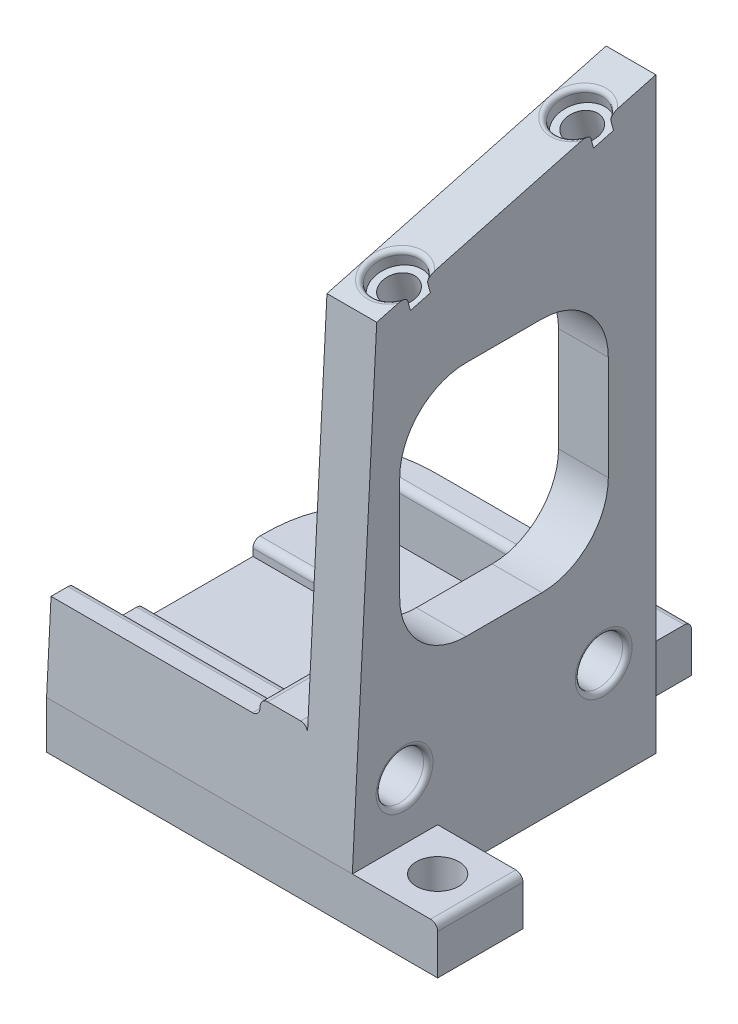
SolidWorks part; units mm, degrees
ref_plane "Front" through (0, 0, 0) normal (0, 0, 1) x (1, 0, 0)
ref_plane "Top" through (0, 0, 0) normal (0, 1, 0) x (1, 0, 0)
ref_plane "Right" through (0, 0, 0) normal (1, 0, 0) x (0, 0, -1)
sketch "Sketch1" plane through (0, 0, 0) normal (1, 0, 0) x (0, 0, -1)
  line L0 (-13.0089, 0) -> (13.0089, 0)
  line L1 (13.0089, 0) -> (13.0089, 8.5)
  line L2 (13.0089, 8.5) -> (5.7589, 8.5)
  line L3 (5.7589, 8.5) -> (5.7589, 7)
  line L4 (5.7589, 7) -> (-5.7589, 7)
  line L5 (-5.7589, 7) -> (-5.7589, 8.5)
  line L6 (-5.7589, 8.5) -> (-13.0089, 8.5)
  line L7 (-13.0089, 8.5) -> (-13.0089, 0)
  dimension "D1" = 8.5
  dimension "D2" = 7.25
  dimension "D3" = 26.0178
  dimension "D4" = 1.5
extrude "Boss-Extrude1" add sketch "Sketch1" along normal mid plane 22
sketch "Sketch3" plane through (0, 0, 0) normal (0, -1, 0) x (1, 0, 0)
  line L1 (-11, -13.0089) -> (11, -13.0089)
  line L2 (-11, -13.0089) -> (-11, -16.0089)
  line L3 (-11, -16.0089) -> (11, -16.0089)
  line L4 (11, -13.0089) -> (11, -16.0089)
  line L5 (-11, 13.0089) -> (11, 13.0089)
  line L6 (-11, 13.0089) -> (-11, 16.0089)
  line L7 (-11, 16.0089) -> (11, 16.0089)
  line L8 (11, 13.0089) -> (11, 16.0089)
  dimension "D1" = 3
  dimension "D2" = 22
  dimension "D3" = 3
  dimension "D4" = 22
extrude "Boss-Extrude2" add sketch "Sketch3" against normal blind 14
sketch "Sketch4" plane through (11, 0, 0) normal (1, 0, 0) x (0, 0, -1)
  line L0 (0, 0) -> (0, 15.7) construction
  line L1 (-16.0089, 0) -> (16.0089, 0) construction
  line L2 (-8.8, 15.7) -> (-16.0089, 15.7)
  line L3 (-16.0089, 14) -> (-16.0089, 0) construction
  line L4 (-16.0089, 15.7) -> (-16.0089, 0)
  line L5 (-16.0089, 0) -> (16.0089, 0)
  line L6 (16.0089, 0) -> (16.0089, 15.7)
  line L7 (16.0089, 14) -> (16.0089, 0) construction
  line L8 (16.0089, 15.7) -> (-8.8, 15.7)
  dimension "D2" = 15.7
extrude "Boss-Extrude3" add sketch "Sketch4" along normal blind 5
sketch "Sketch5" plane through (16, 0, 0) normal (1, 0, 0) x (0, 0, -1)
  line L0 (-16.0089, 11) -> (-10.5, 11) construction
  line L1 (-16.0089, 15.7) -> (-16.0089, 0) construction
  line L2 (-10.5, 11) -> (-10.5, 0) construction
  line L3 (-16.0089, 0) -> (16.0089, 0) construction
  line L4 (0, 0) -> (0, 15.7) construction
  line L5 (16.0089, 15.7) -> (-16.0089, 15.7) construction
  circle A0 centre (-10.5, 11) radius 1.75
  circle A1 centre (10.5, 11) radius 1.75
  dimension "D3" = 3.5
  dimension "D1" = 5.5089
  dimension "D2" = 11
extrude "Cut-Extrude1" cut sketch "Sketch5" against normal through all
sketch "Sketch6" plane through (0, 0, 0) normal (0, -1, 0) x (1, 0, 0)
  line L5 (16, -16.0089) -> (7, -16.0089)
  line L13 (16, -16.0089) -> (16, -25.0089)
  line L14 (16, -25.0089) -> (7, -25.0089)
  line L23 (7, -16.0089) -> (7, -25.0089)
  dimension "D1" = 9
  dimension "D2" = 9
extrude "Boss-Extrude4" add sketch "Sketch6" against normal blind 5
sketch "Sketch10" plane through (0, 0, 0) normal (0, -1, 0) x (1, 0, 0)
  line L1 (16, 16.0089) -> (16, -25.0089) construction
  line L2 (7, -25.0089) -> (16, -25.0089) construction
  line L3 (7, -25.0089) -> (7, -16.0089) construction
  line L4 (7, -16.0089) -> (16, -16.0089) construction
  line L5 (16, -25.0089) -> (16, -16.0089) construction
  line L7 (11.5, -20.5089) -> (7, -20.5089) construction
  line L9 (11.5, -20.5089) -> (11.5, -25.0089) construction
  circle A1 centre (11.5, -20.5089) radius 2.25
  dimension "D1" = 9
  dimension "D2" = 4.5
extrude "Cut-Extrude2" cut sketch "Sketch10" against normal through all
fillet "Fillet1" radius 0.75 11 edges at (0, 8.5, 5.7589) (0, 8.5, -5.7589) (11, 11.25, 13.0089) (11, 11.25, -13.0089) (0, 14, 13.0089) (0, 14, -13.0089) (11, 15.7, 0) (11, 14, 14.5089) (11, 14, -14.5089) (16, 15.7, 0) (11.5, 5, -25.0089)
fillet "Fillet2" radius 10 1 edges at (-11, 7, -16.0089) curvature continuous yes
sketch "Sketch11" plane through (16, 0, 0) normal (1, 0, 0) x (0, 0, -1)
  circle A0 centre (-10.5, 11) radius 2.5
  circle A1 centre (10.5, 11) radius 2.5
  dimension "D1" = 5
extrude "Cut-Extrude3" cut sketch "Sketch11" against normal blind 0.75
sketch "Sketch12" plane through (0, 0, 0) normal (0, -1, 0) x (1, 0, 0)
  line L0 (16, 16.0089) -> (16, -25.0089) construction
  line L1 (25, 16.0089) -> (16, 16.0089)
  line L2 (25, 16.0089) -> (25, -16.0089)
  line L3 (25, -16.0089) -> (16, -16.0089)
  line L4 (16, 16.0089) -> (16, -16.0089)
  line L5 (16, 16.0089) -> (-11, 16.0089) construction
  line L6 (-1, -16.0089) -> (7, -16.0089) construction
  dimension "D1" = 9
extrude "Boss-Extrude5" add sketch "Sketch12" against normal blind 62
sketch "Sketch13" plane through (25, 0, 0) normal (1, 0, 0) x (0, 0, -1)
  line L7 (16.0089, 62) -> (-16.0089, 53.4209)
  line L8 (-16.0089, 62) -> (-16.0089, 0) construction
  line L9 (-16.0089, 53.4209) -> (-16.0089, 62)
  line L10 (-16.0089, 62) -> (16.0089, 62)
  dimension "D1" = 15
extrude "Cut-Extrude4" cut sketch "Sketch13" against normal up to surface (9 mm away) up to face at (16, 38.475, 0)
sketch "Sketch14" plane through (25, 0, 0) normal (1, 0, 0) x (0, 0, -1)
  circle A0 centre (10.5, 11) radius 2.5
  circle A1 centre (-10.5, 11) radius 2.5
  dimension "D1" = 5
extrude "Cut-Extrude5" cut sketch "Sketch14" against normal up to surface (9.75 mm away) up to face at (15.25, 11, 8)
sketch "Sketch15" plane through (0, 53.8446, 14.4276) normal (0, 0.9659, 0.2588) x (1, 0, 0)
  line L0 (19, 5.3629) -> (19, 25.3629) construction
  line L1 (19, 5.3629) -> (19, -1.6371) construction
  line L2 (16, -1.6371) -> (25, -1.6371) construction
  line L3 (19, 5.3629) -> (25, 5.3629) construction
  line L4 (16, -1.6371) -> (16, 31.5102) construction
  line L5 (25, -1.6371) -> (25, 31.5102) construction
  circle A0 centre (19, 5.3629) radius 1.7
  circle A1 centre (19, 25.3629) radius 1.7
  dimension "D1" = 3.4
  dimension "D3" = 3
  dimension "D2" = 20
  dimension "D4" = 7
extrude "Cut-Extrude6" cut sketch "Sketch15" against normal blind 5
sketch "Sketch16" plane through (0, 53.8446, 14.4276) normal (0, 0.9659, 0.2588) x (1, 0, 0)
  circle A0 centre (19, 25.3629) radius 2.5
  circle A1 centre (19, 5.3629) radius 2.5
  dimension "D1" = 5
extrude "Cut-Extrude7" cut sketch "Sketch16" against normal blind 1.6
fillet "Fillet3" radius 0.5 2 edges at (19, 59.7619, -7.6563) (19, 54.5855, 11.6622)
fillet "Fillet4" radius 0.5 2 edges at (25, 11, -13) (25, 11, 8)
ref_plane "Plane2" through (0, 62, 0) normal (0, -1, 0) x (-1, 0, 0)
sketch "Sketch18" plane through (0, 62, 0) normal (0, -1, 0) x (-1, 0, 0)
  line L0 (-16, -16.0089) -> (-25, -16.0089) construction
  line L1 (-25, 16.0089) -> (-21.25, 16.0089)
  line L2 (-25, 16.0089) -> (-25, -16.0089)
  line L3 (-25, -16.0089) -> (-21.25, -16.0089)
  line L4 (-21.25, 16.0089) -> (-21.25, -16.0089)
  dimension "D1" = 3.75
extrude "Cut-Extrude8" cut sketch "Sketch18" along normal through all
fillet "Fillet5" radius 0.5 2 edges at (21.25, 11, -13) (21.25, 11, 8)
sketch "Sketch19" plane through (0, 0, 0) normal (0, -1, 0) x (1, 0, 0)
  line L1 (21.25, 16.0089) -> (30.25, 16.0089)
  line L2 (21.25, 16.0089) -> (21.25, 7.0089)
  line L3 (21.25, 7.0089) -> (30.25, 7.0089)
  line L4 (30.25, 16.0089) -> (30.25, 7.0089)
  dimension "D1" = 9
  dimension "D2" = 9
extrude "Boss-Extrude6" add sketch "Sketch19" against normal blind 5
sketch "Sketch20" plane through (0, 5, 0) normal (0, 1, 0) x (1, 0, 0)
  line L0 (25.75, -11.5089) -> (21.25, -11.5089) construction
  line L1 (21.25, -16.0089) -> (21.25, -7.0089) construction
  line L2 (25.75, -11.5089) -> (25.75, -7.0089) construction
  line L3 (21.25, -7.0089) -> (30.25, -7.0089) construction
  circle A0 centre (25.75, -11.5089) radius 2.25
  dimension "D1" = 4.5
extrude "Cut-Extrude9" cut sketch "Sketch20" against normal up to next
fillet "Fillet6" radius 0.75 1 edges at (30.25, 5, 11.5089)
sketch "Sketch21" plane through (16, 0, 0) normal (-1, 0, 0) x (0, 0, 1)
  line L1 (11.0089, 20.7) -> (-10.9911, 20.7)
  line L2 (11.0089, 20.7) -> (11.0089, 45.7)
  line L3 (11.0089, 45.7) -> (-10.9911, 45.7)
  line L4 (-10.9911, 20.7) -> (-10.9911, 45.7)
  line L6 (-16.0089, 15.7) -> (16.0089, 15.7) construction
  line L7 (16.0089, 53.4209) -> (16.0089, 14.95) construction
  dimension "D1" = 5
  dimension "D2" = 22
  dimension "D3" = 25
  dimension "D4" = 5
extrude "Cut-Extrude10" cut sketch "Sketch21" against normal up to next
sketch "Sketch22" plane through (21.25, 0, 0) normal (1, 0, 0) x (0, 0, -1)
  line L0 (-16.0089, 53.4209) -> (-16.0089, 5)
  line L1 (-16.0089, 5) -> (-13.4351, 54.1105)
  line L2 (-11.1641, 54.719) -> (-16.0089, 53.4209) construction
  line L3 (-13.4351, 54.1105) -> (-16.0089, 53.4209)
  dimension "D1" = 3
extrude "Cut-Extrude11" cut sketch "Sketch22" against normal through all
fillet "Fillet8" radius 7 4 edges at (18.625, 20.7, 11.0089) (18.625, 20.7, -10.9911) (18.625, 45.7, 11.0089) (18.625, 45.7, -10.9911)
